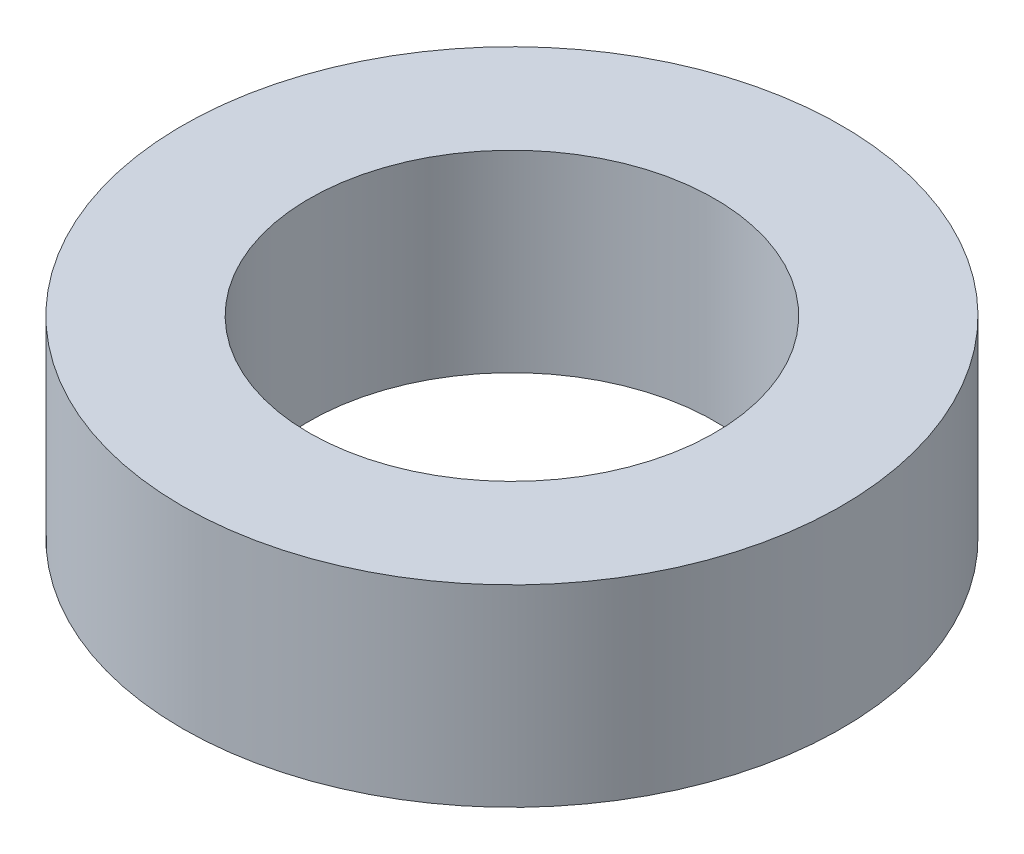
SolidWorks part; units mm, degrees
ref_plane "Front Plane" through (0, 0, 0) normal (0, 0, 1) x (1, 0, 0)
ref_plane "Top Plane" through (0, 0, 0) normal (0, 1, 0) x (1, 0, 0)
ref_plane "Right Plane" through (0, 0, 0) normal (1, 0, 0) x (0, 0, -1)
sketch "Sketch1" plane through (0, 0, 0) normal (0, 1, 0) x (1, 0, 0)
  circle A0 centre (0, 0) radius 32.5
  dimension "FLANGE_OD" = 65
extrude "Boss-Extrude1" add sketch "Sketch1" along normal blind 19
sketch "Sketch2" plane through (0, 0, 0) normal (0, 1, 0) x (1, 0, 0)
  circle A0 centre (0, 0) radius 20
  dimension "BORE_D" = 40
extrude "Cut-Extrude1" cut sketch "Sketch2" along normal through all
sketch "Sketch3" plane through (0, 19, 0) normal (0, 1, 0) x (1, 0, 0)
  circle A0 centre (0, 0) radius 13.5193 construction
  circle A1 centre (-13.5193, 0) radius 2.1729
  dimension "BOLT_D" = 4.3458
  dimension "BOLT_PCD" = 27.0386
extrude "Cut-Extrude2" cut sketch "Sketch3" against normal blind 16.7893 rebuild error yes
pattern_circular "CirPattern1" count 5 over 360 rebuild error yes
